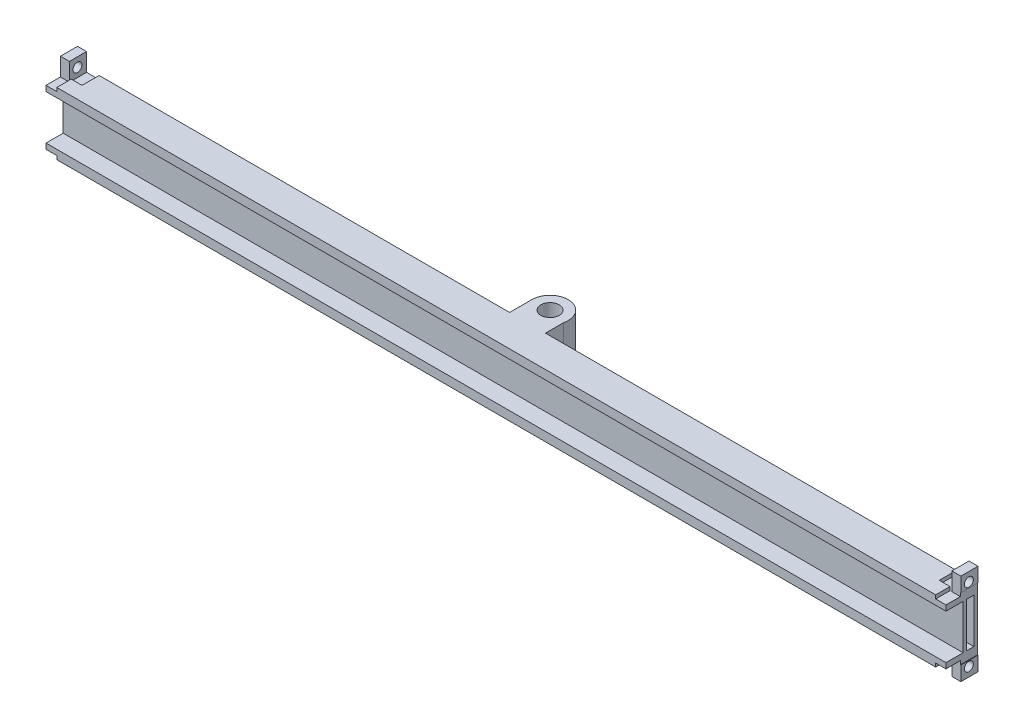
SolidWorks part; units mm, degrees
material "PLA"
ref_plane "Front Plane" through (0, 0, 0) normal (1, 0, 0) x (0, 1, 0)
ref_plane "Top Plane" through (0, 0, 0) normal (0, 0, 1) x (0, 1, 0)
ref_plane "Right Plane" through (0, 0, 0) normal (0, 1, 0) x (-1, 0, 0)
sketch "Sketch1" plane through (0, 0, 0) normal (1, 0, 0) x (0, 1, 0)
  line L16 (0, 4.7625) -> (-2.5, 4.7625)
  line L17 (0, 0) -> (12.3825, 0)
  line L18 (0, 0) -> (0, 4.7625)
  line L19 (0, 4.7625) -> (12.3825, 4.7625) construction
  line L20 (12.3825, 0) -> (12.3825, 4.7625)
  line L21 (-2.5, 4.7625) -> (-2.5, -4)
  line L22 (-2.5, -4) -> (14.8825, -4)
  line L23 (14.8825, -4) -> (14.8825, 4.7625)
  line L24 (12.3825, 4.7625) -> (14.8825, 4.7625)
  dimension "D1" = 4.7625
  dimension "D2" = 12.3825
  dimension "D3" = 2.5
extrude "Boss-Extrude1" add sketch "Sketch1" along normal blind 250
sketch "Sketch3" plane through (0, -2.5, 0) normal (0, -1, 0) x (1, 0, 0)
  line L0 (120.0194, -4) -> (129.9806, -4)
  line L1 (250, -4) -> (0, -4) construction
  line L2 (129.9806, -4) -> (129.9806, -9)
  line L3 (120.0194, -4) -> (120.0194, -10.1759)
  line L4 (0, 4.7625) -> (0, -4) construction
  arc A0 (120.0194, -10.1759) -> (129.9806, -9) centre (125.0694, -10.1759) ccw
  circle A1 centre (125.0694, -10.1759) radius 2.55
  point P5 (125, -4)
  dimension "D2" = 5.1
  dimension "D3" = 5
  dimension "D4" = 125
extrude "Boss-Extrude2" add sketch "Sketch3" against normal up to surface (17.3825 mm away) up to face at (125, 14.8825, 0.3813)
sketch "Sketch6" plane through (0, -2.5, 0) normal (0, -1, 0) x (1, 0, 0)
  line L0 (120.0194, -4) -> (0, -4) construction
  line L1 (117.5385, -4) -> (131.3691, -4)
  line L2 (117.5385, -4) -> (117.5385, -13.6365)
  line L3 (117.5385, -13.6365) -> (131.3691, -13.6365)
  line L4 (131.3691, -4) -> (131.3691, -13.6365)
extrude "Cut-Extrude2" [suppressed] cut sketch "Sketch6" against normal blind 5
sketch "Sketch7" plane through (0, 14.8825, 0) normal (0, 1, 0) x (-1, 0, 0)
  line L0 (-250, -4) -> (-129.9806, -4) construction
  line L1 (-136.5723, -4) -> (-116.3235, -4)
  line L2 (-136.5723, -4) -> (-136.5723, -14.7915)
  line L3 (-136.5723, -14.7915) -> (-116.3235, -14.7915)
  line L4 (-116.3235, -4) -> (-116.3235, -14.7915)
extrude "Cut-Extrude3" [suppressed] cut sketch "Sketch7" against normal blind 5
sketch "Sketch8" plane through (250, 0, 0) normal (1, 0, 0) x (0, 1, 0)
  line L0 (6.1913, 0) -> (6.1913, -4) construction
  line L5 (12.3825, 0) -> (0, 0) construction
  line L6 (14.8825, -4) -> (-2.5, -4) construction
  line L11 (0, -3) -> (12.3825, -3)
  line L12 (0, -3) -> (0, -1)
  line L13 (0, -1) -> (12.3825, -1)
  line L14 (12.3825, -3) -> (12.3825, -1)
  line L15 (0, -3) -> (12.3825, -1) construction
  line L16 (0, -1) -> (12.3825, -3) construction
  point P6 (6.1913, -2)
  dimension "D1" = 12.3825
extrude "Cut-Extrude4" cut sketch "Sketch8" against normal through all
sketch "Sketch9" plane through (0, 0, -4) normal (0, 0, -1) x (-1, 0, 0)
  line L0 (-117.5194, -2.5) -> (-117.5194, 14.8825) construction
  line L1 (-120.0194, -2.5) -> (0, -2.5) construction
  line L2 (-120.0194, 14.8825) -> (0, 14.8825) construction
  line L3 (-120.0194, 14.8825) -> (-120.0194, -2.5) construction
  line L4 (-116.5194, 12.3825) -> (-118.5194, 12.3825)
  line L5 (-116.5194, 12.3825) -> (-116.5194, 0)
  line L6 (-116.5194, 0) -> (-118.5194, 0)
  line L7 (-118.5194, 12.3825) -> (-118.5194, 0)
  line L8 (-116.5194, 12.3825) -> (-118.5194, 0) construction
  line L9 (-116.5194, 0) -> (-118.5194, 12.3825) construction
  point P6 (-117.5194, 6.1913)
  dimension "D3" = 2.5
  dimension "D1" = 12.3825
extrude "Cut-Extrude5" cut sketch "Sketch9" against normal up to next
ref_plane "Plane1" through (125.0694, 0, 0) normal (-1, 0, 0) x (0, 0, 1)
mirror "Mirror1" about plane through (125.0694, 0, 0) normal (-1, 0, 0) of "Cut-Extrude5"
sketch "Sketch10" plane through (0, 0, 4.7625) normal (0, 0, 1) x (1, 0, 0)
  line L1 (0, 14.8825) -> (2.5, 14.8825)
  line L2 (0, 14.8825) -> (0, 18.8912)
  line L3 (0, 18.8912) -> (2.5, 18.8912)
  line L4 (2.5, 14.8825) -> (2.5, 18.8912)
  line L5 (0, -2.5) -> (2.5, -2.5)
  line L6 (0, -2.5) -> (0, -6.5088)
  line L7 (0, -6.5088) -> (2.5, -6.5088)
  line L8 (2.5, -2.5) -> (2.5, -6.5088)
  dimension "D2" = 25.4
extrude "Boss-Extrude3" add sketch "Sketch10" against normal up to surface (8.7625 mm away) up to face at (117.5194, 6.1913, -4)
mirror "Mirror2" about plane through (125.0694, 0, 0) normal (-1, 0, 0) of "Boss-Extrude3"
sketch "Sketch11" plane through (250.1388, 0, 0) normal (1, 0, 0) x (0, 1, 0)
  circle A0 centre (16.3512, -1.46) radius 1.25 construction
  circle A1 centre (-3.9687, -1.46) radius 1.25 construction
  circle A2 centre (16.3512, -1.46) radius 1.25
  circle A3 centre (-3.9687, -1.46) radius 1.25
extrude "Cut-Extrude6" cut sketch "Sketch11" against normal up to surface (2.5 mm away) up to face at (247.6388, 16.8869, 0.3813)
mirror "Mirror3" about plane through (125.0694, 0, 0) normal (-1, 0, 0) of "Cut-Extrude6"
sketch "Sketch14" plane through (0, 0, 4.7625) normal (0, 0, 1) x (1, 0, 0)
  line L0 (0, 6.1912) -> (17.1619, 6.1912) construction
  line L1 (0, -6.5088) -> (3, -6.5088)
  line L2 (0, -6.5088) -> (0, -1.5088)
  line L3 (0, -1.5088) -> (3, -1.5088)
  line L4 (3, -6.5088) -> (3, -1.5088)
  line L5 (0, 12.3825) -> (0, 0) construction
  line L6 (0, 13.8912) -> (3, 13.8912)
  line L7 (3, 18.8912) -> (3, 13.8912)
  line L8 (0, 18.8912) -> (3, 18.8912)
  line L9 (0, 18.8912) -> (0, 13.8912)
  dimension "D2" = 3
extrude "Cut-Extrude7" cut sketch "Sketch14" against normal blind 4
mirror "Mirror4" about plane through (125.0694, 0, 0) normal (-1, 0, 0) of "Cut-Extrude7"
sketch "Sketch15" plane through (0, -2.5, 0) normal (0, -1, 0) x (-1, 0, 0)
  line L0 (-3, -0.7625) -> (-2.5, -0.7625) construction
  line L1 (-2.5, 4) -> (-6, 4)
  line L2 (-2.5, 4) -> (-2.5, -0.7625)
  line L3 (-2.5, -0.7625) -> (-6, -0.7625)
  line L4 (-6, 4) -> (-6, -0.7625)
  line L5 (0, 4) -> (0, -0.7625) construction
  dimension "D1" = 6
extrude "Cut-Extrude9" cut sketch "Sketch15" against normal blind 1 contours L4 L3 L2 L1
ref_plane "Plane3" through (0, 6.1913, 0) normal (0, 1, 0) x (1, 0, 0)
mirror "Mirror7" about plane through (0, 6.1913, 0) normal (0, 1, 0) of "Cut-Extrude9"
mirror "Mirror8" about plane through (125.0694, 0, 0) normal (-1, 0, 0) of "Mirror7"
equation "\"D1@Sketch1\"=\"ball_diameter\" * 0.25"
equation "\"D2@Sketch1\"=\"ball_diameter\" * 0.65"
equation "\"D3@Sketch1\"=\"wall_thickness\""
equation "\"D4@Sketch1\"=0.4cm"
equation "\"D1@Boss-Extrude1\"=\"track_length\""
equation "\"D2@Sketch3\"=\"axle\" + 0.01"
equation "\"ball_diameter\"= 0.75in"
equation "\"wall_thickness\" = 0.25cm"
equation "\"track_length\" = 25cm"
equation "\"axle\" = 5mm"
equation "\"D3@Sketch3\"=\"axle\" * 1"
equation "\"D4@Sketch3\"=\"track_length\" / 2"
equation "\"pillar_width\" = 2.75cm"
equation "\"D1@Sketch9\"=\"ball_diameter\" * 0.65"
equation "\"D1@Sketch8\"=\"ball_diameter\"*0.65"
equation "\"D1@Sketch10\"=\"wall_thickness\""
equation "\"D2@Sketch14\"=0.3"
